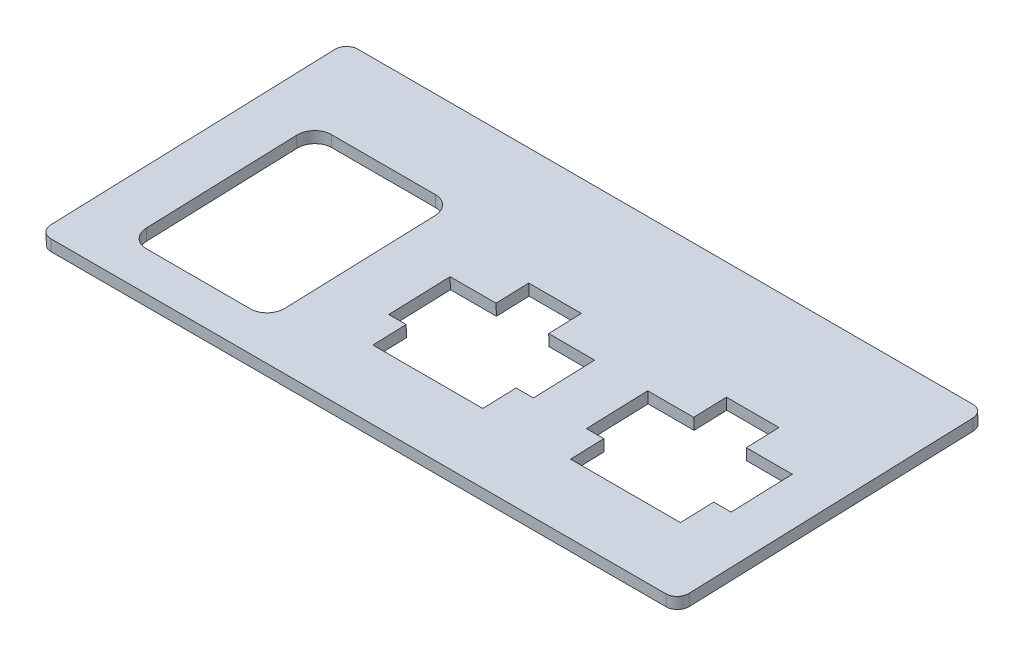
SolidWorks part; units mm, degrees
ref_plane "Front Plane" through (0, 0, 0) normal (0, 0, 1) x (1, 0, 0)
ref_plane "Top Plane" through (0, 0, 0) normal (0, 1, 0) x (1, 0, 0)
ref_plane "Right Plane" through (0, 0, 0) normal (1, 0, 0) x (0, 0, -1)
sketch "Sketch1" plane through (0, -71.9872, -2.5138) normal (0, 0.9994, 0.0349) x (1, 0, 0)
  line L1 (-53.6759, -2.9116) -> (-56.175, -2.9116) construction
  line L2 (55.275, 48.6897) -> (-55.275, 48.6897) construction
  line L8 (-55.175, -4.4116) -> (55.175, -4.4116)
  line L9 (55.175, -4.4116) -> (55.175, 48.6897)
  line L10 (55.175, 48.6897) -> (-55.175, 48.6897)
  line L11 (-55.175, 48.6897) -> (-55.175, -4.4116)
  dimension "D1" = 1.5
  dimension "D2" = 3.0034
  dimension "D3" = 3.0034
extrude "Boss-Extrude1" add sketch "Sketch1" along normal blind 2
sketch "Sketch2" plane through (0, -71.9872, -2.5138) normal (0, -0.9994, -0.0349) x (1, 0, 0)
  line L0 (-4.05, -23.4641) -> (-4.05, -29.1141)
  line L1 (-43.175, -2.1141) -> (-25.175, -2.1141)
  line L2 (-46.175, -5.1141) -> (-46.175, -31.1141)
  line L3 (-43.175, -34.1141) -> (-25.175, -34.1141)
  line L4 (-22.175, -5.1141) -> (-22.175, -31.1141)
  line L5 (-12, -12.8641) -> (-9, -12.8641)
  line L6 (-12, -12.8641) -> (-12, -23.4641)
  line L7 (-12, -23.4641) -> (-4.05, -23.4641)
  line L8 (13, -12.8641) -> (13, -23.4641)
  line L9 (-9, -7.1141) -> (10, -7.1141)
  line L10 (-9, -7.1141) -> (-9, -12.8641)
  line L11 (-4.05, -29.1141) -> (5.05, -29.1141)
  line L12 (10, -7.1141) -> (10, -12.8641)
  line L13 (10, -12.8641) -> (13, -12.8641)
  line L14 (5.05, -23.4641) -> (5.05, -29.1141)
  line L15 (5.05, -23.4641) -> (13, -23.4641)
  line L16 (-13, -4.6141) -> (14, -31.6141) construction
  line L17 (-13, -4.6141) -> (14, -4.6141) construction
  line L18 (-13, -4.6141) -> (-13, -31.6141) construction
  line L19 (-13, -31.6141) -> (14, -31.6141) construction
  line L20 (14, -4.6141) -> (14, -31.6141) construction
  line L21 (17.5875, 3.7502) -> (17.5875, -36.664) construction
  line L22 (47.175, -18.1641) -> (22.175, -18.1641) construction
  line L23 (34.675, -7.1141) -> (34.675, -29.1141) construction
  line L24 (21.175, -4.6141) -> (21.175, -31.6141) construction
  line L25 (48.175, -31.6141) -> (21.175, -31.6141) construction
  line L26 (48.175, -4.6141) -> (48.175, -31.6141) construction
  line L27 (48.175, -4.6141) -> (21.175, -4.6141) construction
  line L28 (-48.175, -18.1141) -> (-46.175, -18.1141) construction
  line L29 (-48.175, -0.1141) -> (-20.175, -0.1141) construction
  line L30 (-48.175, -0.1141) -> (-48.175, -36.1141) construction
  line L31 (-48.175, -36.1141) -> (-20.175, -36.1141) construction
  line L32 (-20.175, -0.1141) -> (-20.175, -36.1141) construction
  line L33 (-34.175, -2.1141) -> (-34.175, -0.1141) construction
  line L34 (0.5, -7.1141) -> (0.5, -29.1141) construction
  line L35 (-12, -18.1641) -> (13, -18.1641) construction
  line L36 (48.175, -4.6141) -> (21.175, -31.6141) construction
  line L37 (30.125, -23.4641) -> (22.175, -23.4641)
  line L38 (30.125, -23.4641) -> (30.125, -29.1141)
  line L39 (25.175, -12.8641) -> (22.175, -12.8641)
  line L40 (25.175, -7.1141) -> (25.175, -12.8641)
  line L41 (39.225, -29.1141) -> (30.125, -29.1141)
  line L42 (44.175, -7.1141) -> (44.175, -12.8641)
  line L43 (44.175, -7.1141) -> (25.175, -7.1141)
  line L44 (22.175, -12.8641) -> (22.175, -23.4641)
  line L45 (47.175, -23.4641) -> (39.225, -23.4641)
  line L46 (47.175, -12.8641) -> (47.175, -23.4641)
  line L47 (47.175, -12.8641) -> (44.175, -12.8641)
  line L48 (39.225, -23.4641) -> (39.225, -29.1141)
  line L49 (21.175, -18.1141) -> (14, -18.1141) construction
  line L50 (-55.175, 4.4116) -> (55.175, 4.4116) construction
  line L51 (48.175, -18.1141) -> (52.175, -18.1141) construction
  line L52 (55.175, 4.4116) -> (55.175, -48.6897) construction
  line L53 (-46.7914, -40.6398) -> (46.7914, -40.6398) construction
  line L54 (-13, -18.1141) -> (-20.175, -18.1141) construction
  line L55 (-34.175, -0.1141) -> (-34.175, 4.4116) construction
  line L56 (-34.175, -36.1141) -> (-34.175, -40.6398) construction
  line L57 (-55.175, -48.6897) -> (-55.175, 4.4116) construction
  line L58 (-48.175, -18.1141) -> (-52.175, -18.1141) construction
  arc A0 (-46.175, -31.1141) -> (-43.175, -34.1141) centre (-43.175, -31.1141) ccw
  arc A1 (-25.175, -34.1141) -> (-22.175, -31.1141) centre (-25.175, -31.1141) ccw
  arc A2 (-25.175, -2.1141) -> (-22.175, -5.1141) centre (-25.175, -5.1141) cw
  arc A3 (-43.175, -2.1141) -> (-46.175, -5.1141) centre (-43.175, -5.1141) ccw
  point P28 (0.5, -18.1141)
  point P63 (34.675, -18.1141)
  dimension "D1" = 3
  dimension "D2" = 32
  dimension "D3" = 24
  dimension "D4" = 28
  dimension "D5" = 36
  dimension "D6" = 25
  dimension "D7" = 22
  dimension "D8" = 10.6
  dimension "D9" = 19
  dimension "D10" = 9.1
  dimension "D11" = 5.75
  dimension "D12" = 27
  dimension "D13" = 27
  dimension "D14" = 4
  dimension "D15" = 3
  dimension "D16" = 3
extrude "Cut-Extrude1" cut sketch "Sketch2" against normal up to next
fillet "Fillet1" radius 2 4 edges at (-55.175, -71.1418, 1.93) (55.175, -71.1418, 1.93) (55.175, -69.2886, -51.139) (-55.175, -69.2886, -51.139)
